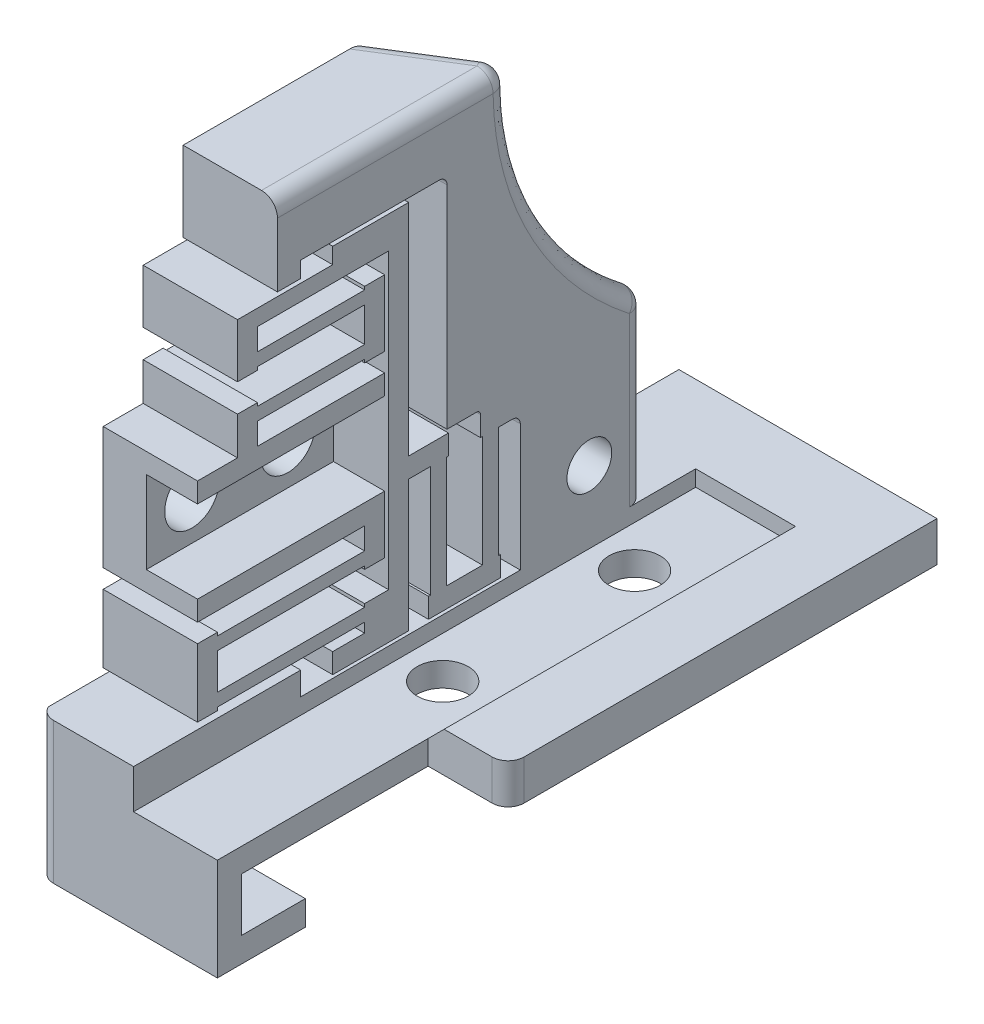
SolidWorks part; units mm, degrees
other "Markup1"
sketch "Sketch8" plane through (10.5, 0, 3) normal (0.7095, 0.0467, 0.7031) x (0.7044, -0.0184, -0.7096)
ref_plane "Front Plane" through (0, 0, 0) normal (0, 0, 1) x (1, 0, 0)
ref_plane "Top Plane" through (0, 0, 0) normal (0, 1, 0) x (1, 0, 0)
ref_plane "Right Plane" through (0, 0, 0) normal (1, 0, 0) x (0, 0, -1)
sketch "Sketch1" plane through (0, 0, 0) normal (1, 0, 0) x (0, 0, -1)
  line L0 (-1.25, -12.7333) -> (6.7, -12.7333)
  line L1 (6.7, -12.7333) -> (6.7, -22.75)
  line L2 (-5, -12.7333) -> (-5, -20.3833)
  line L3 (-5, -20.3833) -> (5.45, -20.3833)
  line L57 (-3.75, -22.55) -> (-3.75, -24.8)
  line L58 (-3.75, -24.8) -> (5.45, -24.8)
  line L60 (5.45, -20.3833) -> (5.45, -21.75)
  line L62 (-5, -21.55) -> (-5, -25.8)
  line L64 (6.95, -6.25) -> (6.95, -24.6)
  line L65 (-1.25, -11.3667) -> (5.45, -11.3667)
  line L66 (5.45, -10.5667) -> (5.45, -8.4167)
  line L68 (-2.5, -8.6167) -> (-2.5, -5.25)
  line L69 (-1.25, -12.7333) -> (-1.25, -11.3667)
  line L71 (6.7, -11.5667) -> (6.7, -7.4167)
  line L73 (-1.25, -7.6167) -> (-1.25, -6.25)
  line L74 (-1.25, -6.25) -> (6.95, -6.25)
  line L75 (-2.5, -5.25) -> (3.45, -5.25)
  line L79 (5.45, -11.3667) -> (5.45, -11.5667)
  line L80 (5.45, -11.5667) -> (6.7, -11.5667)
  line L85 (5.45, -10.5667) -> (-1.25, -10.5667)
  line L86 (-1.25, -10.5667) -> (-1.25, -10.3667)
  line L87 (-1.25, -10.3667) -> (-2.5, -10.3667)
  line L90 (5.45, -8.4167) -> (-1.25, -8.4167)
  line L91 (-1.25, -8.4167) -> (-1.25, -8.6167)
  line L92 (-1.25, -8.6167) -> (-2.5, -8.6167)
  line L93 (-1.25, -7.6167) -> (5.45, -7.6167)
  line L98 (5.45, -7.6167) -> (5.45, -7.4167)
  line L99 (5.45, -7.4167) -> (6.7, -7.4167)
  line L102 (5.45, -21.75) -> (-3.75, -21.75)
  line L103 (-3.75, -21.75) -> (-3.75, -21.55)
  line L104 (-3.75, -21.55) -> (-5, -21.55)
  line L105 (6.7, -22.75) -> (5.45, -22.75)
  line L106 (5.45, -22.75) -> (5.45, -22.55)
  line L111 (5.45, -22.55) -> (-3.75, -22.55)
  line L115 (5.45, -24.8) -> (5.45, -24.6)
  line L116 (5.45, -24.6) -> (6.95, -24.6)
  line L117 (-5, -25.8) -> (-3.75, -25.8)
  line L118 (-3.75, -25.8) -> (-3.75, -25.6)
  line L119 (-3.75, -25.6) -> (5.45, -25.6)
  line L124 (5.45, -25.6) -> (5.45, -26.2)
  line L126 (5.45, -26.2) -> (3.45, -26.2)
  line L127 (3.45, -26.2) -> (3.45, -27.45)
  line L128 (3.45, -27.45) -> (8.2, -27.45)
  line L130 (12.8167, -26.2) -> (10.5667, -26.2)
  line L131 (10.5667, -26.2) -> (10.5667, -19.2333)
  line L136 (10.5667, -19.2333) -> (10.6917, -19.2333)
  line L141 (12.8167, -19.2333) -> (12.8167, -26.2)
  line L145 (9.5667, -26.2) -> (9.4417, -26.2)
  line L146 (9.5667, -26.2) -> (9.5667, -19.2333)
  line L150 (9.5667, -19.2333) -> (8.2, -19.2333)
  line L153 (8.2, -17.9833) -> (10.6917, -17.9833)
  line L155 (14.6833, -19.2333) -> (13.8167, -19.2333)
  line L160 (13.8167, -19.2333) -> (13.8167, -26.2)
  line L168 (15.1833, -27.7) -> (15.1833, -19.7333)
  line L179 (15.1833, -27.7) -> (1.45, -27.7)
  line L180 (1.45, -27.7) -> (1.45, -26.2)
  line L181 (1.45, -26.2) -> (-9, -26.2)
  line L184 (-9, -30.15) -> (23, -30.15)
  line L187 (23, 0) -> (0, 0)
  line L189 (8.2, -27.45) -> (8.2, -19.2333)
  line L190 (1.45, -5) -> (0, -5)
  line L191 (0, -5) -> (0, 0)
  line L192 (13.9417, -26.2) -> (13.8167, -26.2)
  line L193 (12.4417, -17.7333) -> (10.6, -17.7333)
  line L194 (10.6, -17.7333) -> (10.6, -4.5)
  line L198 (9.4417, -26.2) -> (9.4417, -27.45)
  line L199 (13.9417, -26.2) -> (13.9417, -27.45)
  line L200 (13.9417, -27.45) -> (9.4417, -27.45)
  line L201 (8.2, -17.9833) -> (8.2, -4.25)
  line L203 (12.6917, -19.2333) -> (12.6917, -17.9833)
  line L204 (10.6917, -19.2333) -> (10.6917, -17.9833)
  line L205 (12.6917, -19.2333) -> (12.8167, -19.2333)
  line L212 (-9, -30.15) -> (-9, -26.2)
  line L214 (-2.5, -12.7333) -> (-5, -12.7333)
  line L215 (-2.5, -12.7333) -> (-2.5, -10.3667)
  line L216 (23, 0) -> (23, -30.15)
  line L217 (1.45, -5) -> (1.45, -4)
  line L218 (1.45, -4) -> (10.1, -4)
  line L219 (3.45, -5.25) -> (3.45, -4.25)
  line L220 (3.45, -4.25) -> (8.2, -4.25)
  line L221 (13.8167, -19.2333) -> (15.1833, -19.2333) construction
  arc A4 (14.6833, -19.2333) -> (15.1833, -19.7333) centre (14.6833, -19.7333) cw
  arc A5 (12.6917, -17.9833) -> (12.4417, -17.7333) centre (12.4417, -17.9833) ccw
  arc A6 (10.1, -4) -> (10.6, -4.5) centre (10.1, -4.5) cw
  circle A7 centre (3.85, -16.5583) radius 1.7
  circle A8 centre (-2.15, -16.5583) radius 1.7
  circle A9 centre (-2.15, -16.5583) radius 2.85 construction
  circle A10 centre (3.85, -16.5583) radius 2.85 construction
  point P120 (10.6, -5)
  point P140 (15.1833, -19.2333)
  point P144 (12.6917, -17.7333)
  point P151 (-5, -16.5583)
  point P159 (-1.875, -8.6167)
  dimension "D61" = 0.5
  dimension "D62" = 0.25
  dimension "D66" = 0.5
  dimension "D67" = 3.4
  dimension "D68" = 5.7
  dimension "D3" = 4.25
  dimension "D4" = 0.2
  dimension "D6" = 0.8
  dimension "D9" = 0.8
  dimension "D10" = 1.1667
  dimension "D17" = 0.8
  dimension "D18" = 1.75
  dimension "D21" = 0.8
  dimension "D23" = 1
  dimension "D24" = 0.25
  dimension "D37" = 1.25
  dimension "D40" = 0.25
  dimension "D44" = 1
  dimension "D12" = 7.65
  dimension "D20" = 1.25
  dimension "D26" = 1.25
  dimension "D28" = 0.25
  dimension "D33" = 1.25
  dimension "D49" = 2.4
  dimension "D50" = 0.25
  dimension "D31" = 5
  dimension "D54" = 5
  dimension "D55" = 1.25
  dimension "D65" = 2.5
  dimension "D64" = 2.5
  dimension "D29" = 2
  dimension "D52" = 0.25
  dimension "D56" = 1
  dimension "D69" = 6
  dimension "D39" = 4
  dimension "D51" = 32
  dimension "D22" = 1.1667
  dimension "D53" = 2
  dimension "D19" = 0.2
  dimension "D7" = 0.4
  dimension "D8" = 1.45
  dimension "D11" = 1
  dimension "D13" = 4.5
  dimension "D14" = 2
  dimension "D15" = 30.15
  dimension "D16" = 1.25
  dimension "D25" = 1.25
extrude "Boss-Extrude1" add sketch "Sketch1" along normal blind 6
sketch "Sketch2" plane through (0, 0, 5) normal (0, 0, 1) x (1, 0, 0)
  line L0 (6, -12.7333) -> (6, -20.3833) construction
  line L1 (6, -19.1333) -> (2.8, -19.1333)
  line L2 (6, -19.1333) -> (6, -13.9833)
  line L3 (6, -13.9833) -> (2.8, -13.9833)
  line L4 (2.8, -19.1333) -> (2.8, -13.9833)
  line L5 (6, -12.7333) -> (6, -20.3833) construction
  dimension "D1" = 3.2
  dimension "D2" = 1.25
  dimension "D3" = 1.25
extrude "Cut-Extrude4" cut sketch "Sketch2" against normal up to next
sketch "Sketch3" plane through (0, -30.15, 0) normal (0, -1, 0) x (1, 0, 0)
  line L0 (11.24, -4.18) -> (16.24, -4.18)
  line L1 (0, -31) -> (16.24, -31)
  line L2 (0, -31) -> (0, 9)
  line L4 (11.24, -4.18) -> (11.24, 9)
  line L5 (6, 9) -> (6, -23) construction
  line L7 (16.24, -31) -> (16.24, -4.18)
  line L8 (0, 9) -> (0, -23) construction
  line L9 (11.24, 9) -> (0, 9)
  circle A0 centre (8.6, -7.73) radius 1.6
  circle A1 centre (8.6, -19.73) radius 1.6
  dimension "D3" = 3.2
  dimension "D1" = 13.18
  dimension "D2" = 2.6
  dimension "D4" = 12
  dimension "D5" = 5
  dimension "D6" = 40
  dimension "D7" = 16.73
  dimension "D8" = 11.24
sketch "Sketch7" plane through (0, 0, 0) normal (-1, 0, 0) x (0, 0, 1)
  line L0 (2.5, -12.7333) -> (5, -12.7333) construction
  line L2 (-6.7, -12.7333) -> (-6.7, -22.75) construction
  circle A0 centre (2.15, -16.6083) radius 1.7
  circle A1 centre (-3.85, -16.6083) radius 1.7
  circle A2 centre (2.15, -16.6083) radius 2.85 construction
  circle A3 centre (-3.85, -16.6083) radius 2.85 construction
  dimension "D1" = 3.4
  dimension "D2" = 3.875
  dimension "D5" = 5.7
  dimension "D3" = 6
extrude "Cut-Extrude3" cut sketch "Sketch7" against normal up to next
extrude "Boss-Extrude2" add sketch "Sketch3" against normal blind 2.5
sketch "Sketch12" plane through (0, 0, 9) normal (0, 0, 1) x (1, 0, 0)
  line L0 (6, -26.2) -> (6, -27.65) construction
  line L1 (11.24, -27.65) -> (6, -27.65)
  line L2 (11.24, -27.65) -> (11.24, -28.65)
  line L3 (11.24, -28.65) -> (6, -28.65)
  line L4 (6, -27.65) -> (6, -28.65)
  line L5 (11.24, -27.65) -> (6, -27.65) construction
  dimension "D1" = 1
  dimension "D2" = 5.24
extrude "Cut-Extrude6" cut sketch "Sketch12" against normal blind 35.15
sketch "Sketch14" plane through (0, 0, 0) normal (-1, 0, 0) x (0, 0, 1)
  line L1 (9, -28.7) -> (3.5, -28.7)
  line L2 (9, -28.7) -> (9, -35.03)
  line L3 (9, -35.03) -> (3.5, -35.03)
  line L4 (3.5, -28.7) -> (3.5, -35.03)
  line L5 (-1.45, -26.2) -> (9, -26.2) construction
  line L6 (9, -26.2) -> (9, -30.15) construction
  dimension "D1" = 2.5
  dimension "D2" = 6.33
  dimension "D3" = 5.5
extrude "Boss-Extrude4" add sketch "Sketch14" against normal blind 11.24
sketch "Sketch15" plane through (11.24, 0, 0) normal (1, 0, 0) x (0, 0, -1)
  line L1 (-3.5, -30.15) -> (-7.5, -30.15)
  line L2 (-3.5, -30.15) -> (-3.5, -33.48)
  line L3 (-3.5, -33.48) -> (-7.5, -33.48)
  line L4 (-7.5, -30.15) -> (-7.5, -33.48)
  dimension "D1" = 4
  dimension "D2" = 3.33
extrude "Cut-Extrude7" cut sketch "Sketch15" against normal blind 10.25
ref_plane "Plane2" through (0, 0, 7.1) normal (0, 0, 1) x (1, 0, 0)
ref_axis "Axis1" through (11.24, 27.1504, 7.1) along (0, -1, 0)
mirror "Mirror1" [suppressed] of bodies 111
delete or keep bodies "Body-Delete/Keep 1" [suppressed] type delete bodies bodies 111
ref_plane "Plane1" through (4.8929, 0, -3.0574) normal (-0.848, 0, 0.5299) x (0, -1, 0)
sketch "Sketch10" plane through (4.8929, 0, -3.0574) normal (-0.848, 0, 0.5299) x (0, -1, 0)
  line L0 (30.15, 13.5887) -> (30.15, 7.6324) construction
  line L1 (30.15, 2.9682) -> (30.15, -26.2895) construction
  line L2 (30.15, 12.3167) -> (30.15, -33.4435) construction
  circle A0 centre (0.65, -31.2799) radius 21.5
  dimension "D2" = 43
  dimension "D1" = 43.5966
  dimension "D3" = 29.5
extrude "Cut-Extrude5" cut sketch "Sketch10" against normal blind 25
fillet "Fillet1" radius 1 9 edges at (3.1138, -17.4436, -23) (3, 0, -13.4184) (6, -21.8736, -23) (6, -8.7382, -17.1438) (6, 0, -7.6465) (16.24, -28.9, -4.18) (0.99, -31.815, 7.5) (0, -30.615, 9) (0.495, -30.15, 3.5)
chamfer "Chamfer1" distance 1 angle 45 1 edges at (11.24, -27.65, -15.165)
delete or keep bodies "Body-Delete/Keep 2" [suppressed] type delete bodies bodies 113
sketch "Sketch16" plane through (0, 0, 0) normal (-1, 0, 0) x (0, 0, 1)
  line L0 (-23, -27.65) -> (-31, -27.65) construction
  line L1 (-23, -27.65) -> (-23, -19.2756) construction
  circle A0 centre (-19.5, -24.15) radius 1.4
  dimension "D1" = 2.8
  dimension "D2" = 3.5
  dimension "D3" = 3.5
extrude "Cut-Extrude8" cut sketch "Sketch16" against normal through all
sketch "Sketch17" plane through (0, 0, 0) normal (-1, 0, 0) x (0, 0, 1)
  line L0 (-34.4648, 2.4541) -> (18.4949, 2.4541)
  line L1 (-34.4648, 2.4541) -> (-34.4648, -41.0235)
  line L2 (18.4949, 2.4541) -> (18.4949, -41.0235)
  line L3 (-34.4648, -41.0235) -> (18.4949, -41.0235)
extrude "Cut-Extrude9" cut sketch "Sketch17" against normal blind 0.1
mirror "Mirror2" [suppressed] of bodies 113
mirror "Mirror4" [suppressed]
delete or keep bodies "Body-Delete/Keep 3" [suppressed] type delete bodies bodies 123
equation "\"VerticalFlexureWidth\"= 0.8"
equation "\"VerticalFlexureGap\"= 1"
equation "\"VerticalDoubleFlexureWidth\"= 2 * \"VerticalFlexureWidth\" + \"VerticalFlexureGap\""
equation "\"HorizontalFlexureLength\"= 7"
equation "\"FlexureJointWidth\"= 1.25"
equation "\"HeadHeight\"= 7.5"
equation "\"VerticalFlexureLength\"= 18"
equation "\"MinGap\"=0.25"
equation "\"BaseplateHeight+Tolerance\"= 3.33"
equation "\"HeadWidth\"= 13"
equation "\"HorizontalFlexureWidth\"= 1"
equation "\"HorizontalFlexureGap\"= 1"
equation "\"HorizontalDoubleFlexureWidth\"= 2 * \"HorizontalFlexureWidth\" + \"HorizontalFlexureGap\""
equation "\"FlexureWidth\"=0.85"
equation "\"FlexureWideWidth\"= 1.25"
equation "\"FlexureGap\"=1.75"
equation "\"TwinFlexureWidth\"= \"FlexureGap\" + 2 * \"FlexureWideWidth\""
equation "\"D3@Sketch1\"=\"TwinFlexureWidth\""
equation "\"FlexureNeckWidth\"= ( \"FlexureWideWidth\" - \"FlexureWidth\" ) / 2"
equation "\"D4@Sketch1\"=\"FlexureNeckWidth\""
equation "\"D6@Sketch1\"=\"VerticalFlexureWidth\""
equation "\"D9@Sketch1\"=\"VerticalFlexureWidth\""
equation "\"D10@Sketch1\"=\"FlexureGapEdge\""
equation "\"D21@Sketch1\"=\"VerticalFlexureWidth\""
equation "\"D18@Sketch1\"=\"FlexureGap\""
equation "\"FlexureLength\"= 2"
equation "\"MainSupport\"=1.5"
equation "\"D24@Sketch1\"=\"MinGap\""
equation "\"D37@Sketch1\"=\"FlexureJointWidth\""
equation "\"D40@Sketch1\"=\"MinGap\""
equation "\"D44@Sketch1\"=\"HorizontalFlexureWidth\""
equation "\"D20@Sketch1\"=\"MainSupport\"-0.25"
equation "\"D26@Sketch1\"=\"FlexureJointWidth\""
equation "\"D28@Sketch1\"=\"MinGap\""
equation "\"D33@Sketch1\"=\"FlexureJointWidth\""
equation "\"FlexureGapEdge\"= \"FlexureGap\" * ( 2 / 3 )"
equation "\"D55@Sketch1\"=\"FlexureJointWidth\""
equation "\"FlexurePlateConnectionHeigh\"= 5.15 + 2.5"
equation "\"D12@Sketch1\"=\"FlexurePlateConnectionHeigh\""
equation "\"D52@Sketch1\"=\"MinGap\""
equation "\"D17@Sketch1\"=\"VerticalFlexureWidth\""
equation "\"D22@Sketch1\"=\"FlexureGapEdge\""
equation "\"D19@Sketch1\"=\"FlexureNeckWidth\""
equation "\"D11@Sketch1\"=\"HorizontalFlexureWidth\""
equation "\"D16@Sketch1\"=\"FlexureJointWidth\""
equation "\"D25@Sketch1\"=\"FlexureJointWidth\""
